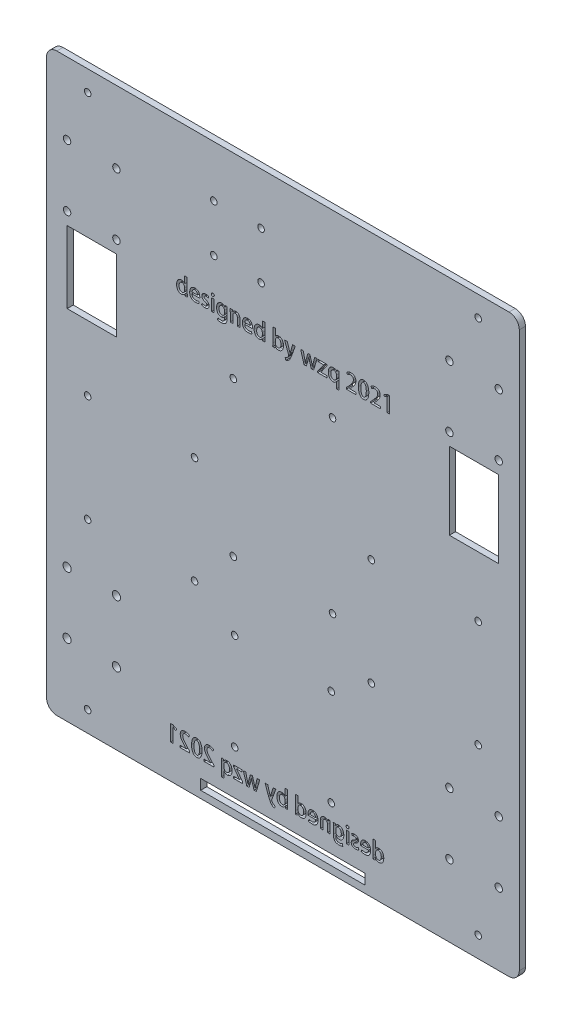
SolidWorks part; units mm, degrees
ref_plane "前视基准面" through (0, 0, 0) normal (0, 0, 1) x (1, 0, 0)
ref_plane "上视基准面" through (0, 0, 0) normal (0, 1, 0) x (1, 0, 0)
ref_plane "右视基准面" through (0, 0, 0) normal (1, 0, 0) x (0, 0, -1)
sketch "草图1" plane through (0, 0, 0) normal (0, 0, 1) x (1, 0, 0)
  line L5 (105, -140) -> (-105, -140)
  line L6 (115, -130) -> (115, 130)
  line L7 (105, 140) -> (-105, 140)
  line L8 (-115, -130) -> (-115, 130)
  line L9 (115, -140) -> (-115, 140) construction
  line L10 (115, 140) -> (-115, -140) construction
  line L14 (81, -105) -> (105, -105) construction
  line L15 (-105, 105) -> (-105, 75) construction
  line L16 (81, -75) -> (81, -105) construction
  line L17 (105, -105) -> (105, -75) construction
  line L18 (-105, 105) -> (-81, 105) construction
  line L19 (-81, 75) -> (-105, 75) construction
  line L20 (-62.3496, 78.399) -> (-62.3496, 78.4642)
  line L21 (-81, 105) -> (-81, 75) construction
  line L22 (-105, -75) -> (-105, -105) construction
  line L23 (105, 105) -> (105, 75) construction
  line L24 (81, 75) -> (105, 75)
  line L25 (81, 105) -> (81, 75)
  line L26 (81, 105) -> (105, 105)
  line L27 (-105, -922.5) -> (-105, 49077.5) construction
  line L32 (-81, -922.5) -> (-81, 49077.5) construction
  line L33 (-95, 2.1864) -> (-95, -49.8136) construction
  line L38 (-105, 68.9565) -> (-81, 68.9565)
  line L39 (-105, 68.9565) -> (-105, 33.9565)
  line L40 (-105, 33.9565) -> (-81, 33.9565)
  line L41 (-81, 68.9565) -> (-81, 33.9565)
  line L42 (-95, -49.8136) -> (-43, -49.8136) construction
  line L43 (-43, 2.1864) -> (-43, -49.8136) construction
  line L44 (-95, 2.1864) -> (-43, 2.1864) construction
  line L45 (-105, 68.9565) -> (49895, 68.9565) construction
  line L46 (81, -925) -> (81, 49075) construction
  line L47 (105, -922.5) -> (105, 49077.5) construction
  line L48 (-1105, 33.9565) -> (48895, 33.9565) construction
  line L49 (81, 68.9565) -> (81, 31.4565)
  line L50 (81, 31.4565) -> (105, 31.4565)
  line L51 (105, 31.4565) -> (105, 68.9565)
  line L52 (105, 68.9565) -> (81, 68.9565)
  line L53 (95, -49.8136) -> (95, 2.1864) construction
  line L54 (43, 2.1864) -> (43, -49.8136) construction
  line L55 (43, -49.8136) -> (95, -49.8136) construction
  line L56 (43, 2.1864) -> (95, 2.1864) construction
  line L57 (0, -1000) -> (0, 49000) construction
  line L58 (-24.13, -30) -> (24.13, -30) construction
  line L59 (24.13, 52.55) -> (24.13, -30) construction
  line L60 (-24.13, 44.93) -> (-24.13, -30) construction
  line L61 (-23.5, -110) -> (23.5, -110) construction
  line L62 (40, -131.5) -> (-40, -131.5)
  line L63 (40, -131.5) -> (40, -136.5)
  line L64 (40, -136.5) -> (-40, -136.5)
  line L65 (-40, -131.5) -> (-40, -136.5)
  line L66 (40, -131.5) -> (-40, -136.5) construction
  line L67 (40, -136.5) -> (-40, -131.5) construction
  line L68 (-23.5, -63) -> (-23.5, -110) construction
  line L69 (-23.5, -63) -> (23.5, -63) construction
  line L70 (23.5, -110) -> (23.5, -63)
  line L71 (-33.6286, 92) -> (-10.6286, 92) construction
  line L72 (-33.6286, 115) -> (-33.6286, 92) construction
  line L73 (-10.6286, 115) -> (-10.6286, 92) construction
  line L74 (-33.6286, 115) -> (-10.6286, 115) construction
  line L75 (-115, 130) -> (-115, 135)
  line L76 (-110, 140) -> (-105, 140)
  line L77 (105, 140) -> (110, 140)
  line L78 (115, 135) -> (115, 130)
  line L79 (-115, -130) -> (-115, -135)
  line L80 (-110, -140) -> (-105, -140)
  line L81 (105, -140) -> (110, -140)
  line L82 (115, -135) -> (115, -130)
  circle A1 centre (-105, -105) radius 2
  circle A2 centre (-105, -75) radius 2
  circle A3 centre (-81, -75) radius 2
  circle A4 centre (-81, -105) radius 2
  circle A5 centre (105, -105) radius 1.8
  circle A6 centre (81, -105) radius 1.8
  circle A7 centre (81, -75) radius 1.8
  circle A8 centre (105, -75) radius 1.8
  circle A9 centre (-105, 105) radius 1.8
  circle A10 centre (-105, 75) radius 1.8
  circle A11 centre (-81, 105) radius 1.8
  circle A12 centre (-81, 75) radius 1.8
  circle A13 centre (105, 105) radius 1.8
  circle A14 centre (105, 75) radius 1.8
  circle A15 centre (81, 75) radius 1.8
  circle A16 centre (81, 105) radius 1.8
  circle A17 centre (-95, -130) radius 1.6
  circle A18 centre (95, -130) radius 1.6
  circle A19 centre (95, 130) radius 1.6
  circle A20 centre (-95, 130) radius 1.6
  circle A21 centre (-95, 2.1864) radius 1.6
  circle A22 centre (-43, 2.1864) radius 1.6
  circle A23 centre (-95, -49.8136) radius 1.6
  circle A24 centre (-43, -49.8136) radius 1.6
  circle A25 centre (95, 2.1864) radius 1.6
  circle A26 centre (43, 2.1864) radius 1.6
  circle A27 centre (95, -49.8136) radius 1.6
  circle A28 centre (43, -49.8136) radius 1.6
  circle A29 centre (-24.13, -30) radius 1.6
  circle A30 centre (24.13, -30) radius 1.6
  circle A32 centre (24.13, 52.55) radius 1.6
  circle A33 centre (-24.13, 44.93) radius 1.6
  circle A34 centre (-23.5, -110) radius 1.6
  circle A35 centre (23.5, -110) radius 1.6
  circle A36 centre (-23.5, -63) radius 1.6
  circle A37 centre (23.5, -63) radius 1.6
  circle A38 centre (-33.6286, 92) radius 1.6
  circle A39 centre (-10.6286, 92) radius 1.6
  circle A40 centre (-33.6286, 115) radius 1.6
  circle A41 centre (-10.6286, 115) radius 1.6
  arc A42 (110, 140) -> (115, 135) centre (110, 135) cw
  arc A43 (-115, 135) -> (-110, 140) centre (-110, 135) cw
  arc A44 (-115, -135) -> (-110, -140) centre (-110, -135) ccw
  arc A45 (110, -140) -> (115, -135) centre (110, -135) ccw
  point P0 (0, 0)
  point P102 (0, -134)
  dimension "D3" = 35
  dimension "D9" = 24
  dimension "D10" = 24
  dimension "D11" = 10
  dimension "D12" = 24
  dimension "D16" = 35
  dimension "D18" = 24
  dimension "D20" = 20
  dimension "D22" = 10
  dimension "D24" = 24
  dimension "D26" = 10
  dimension "D28" = 10
  dimension "D30" = 10
  dimension "D32" = 10
  dimension "D21" = 52
  dimension "D36" = 52
  dimension "D37" = 20
  dimension "D38" = 52
  dimension "D39" = 24.13
  dimension "D40" = 82.55
  dimension "D41" = 74.93
  dimension "D45" = 23.5
  dimension "D46" = 23.5
  dimension "D47" = 47
  dimension "D48" = 33
  dimension "D49" = 23
  dimension "D50" = 23
  dimension "D51" = 25
  dimension "D52" = 5
  dimension "D53" = 5
  dimension "D54" = 5
  dimension "D55" = 5
  dimension "D1" = 280
  dimension "D2" = 230
  dimension "D4" = 10
  dimension "27.5" = 30
  dimension "D13" = 30
  dimension "D14" = 35
  dimension "D15" = 30
  dimension "D17" = 10
  dimension "D19" = 30
  dimension "D23" = 35
  dimension "D25" = 30
  dimension "D27" = 20
  dimension "D29" = 20
  dimension "D31" = 20
  dimension "D33" = 20
  dimension "D34" = 35
  dimension "D35" = 30
  dimension "52" = 52
  dimension "24.13" = 24.13
  dimension "D42" = 110
  dimension "D43" = 6
  dimension "D44" = 5
  dimension "80" = 80
extrude "凸台-拉伸2" add sketch "草图1" along normal blind 3 contours L5 L6 L7 L8 A16 A13 A15 A14 A12 A11 A10 A9 A8 A7 A6 A5 A4 A3 A2 A1 region at (-0.0643, -0.5376, 0)
sketch "草图2" plane through (0, 0, 3) normal (0, 0, 1) x (1, 0, 0)
  text T0 "designed by wzq 2021" font "@Adobe 黑体 Std R" height 8
extrude "切除-拉伸1" cut sketch "草图2" against normal through all
sketch "草图3" plane through (0, 0, 0) normal (0, 0, -1) x (-1, 0, 0)
  text T0 "designed by wzq 2021" font "@Adobe 黑体 Std R" height 8
extrude "切除-拉伸2" cut sketch "草图3" against normal through all
sketch "草图4" plane through (0, 0, 3) normal (0, 0, 1) x (1, 0, 0)
sketch "草图5" plane through (0, 0, 3) normal (0, 0, 1) x (1, 0, 0)
